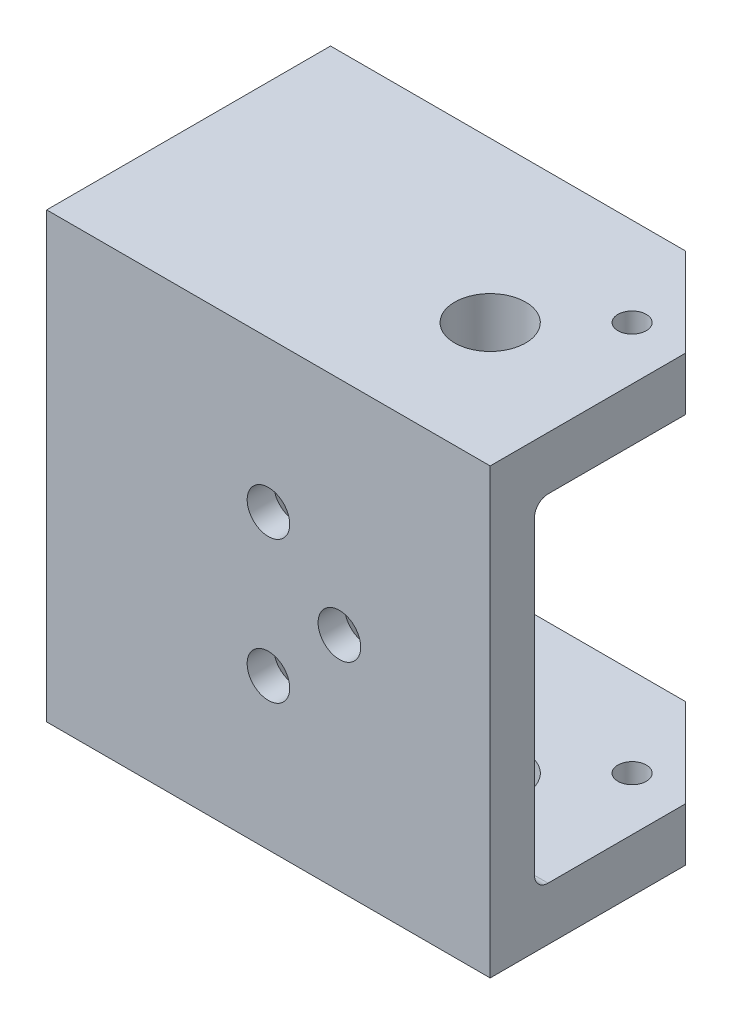
SolidWorks part; units mm, degrees
ref_plane "Front Plane" through (0, 0, 0) normal (0, 0, 1) x (1, 0, 0)
ref_plane "Top Plane" through (0, 0, 0) normal (0, 1, 0) x (1, 0, 0)
ref_plane "Right Plane" through (0, 0, 0) normal (1, 0, 0) x (0, 0, -1)
sketch "Sketch1" plane through (0, 0, 0) normal (0, 0, 1) x (1, 0, 0)
  line L1 (-12.5, 12.5) -> (12.5, 12.5)
  line L2 (-12.5, 12.5) -> (-12.5, -12.5)
  line L3 (-12.5, -12.5) -> (12.5, -12.5)
  line L4 (12.5, 12.5) -> (12.5, -12.5)
  line L5 (-12.5, 12.5) -> (12.5, -12.5) construction
  line L6 (-12.5, -12.5) -> (12.5, 12.5) construction
  point P0 (0, 0)
  dimension "D1" = 25
  dimension "D2" = 25
extrude "Boss-Extrude1" add sketch "Sketch1" along normal blind 2.5
sketch "Sketch2" plane through (0, 0, 0) normal (0, 0, -1) x (-1, 0, 0)
  line L0 (-12.5, -12.5) -> (-12.5, 12.5) construction
  line L1 (12.5, 12.5) -> (-12.5, 12.5)
  line L2 (12.5, 12.5) -> (12.5, 9.5)
  line L3 (12.5, 9.5) -> (-12.5, 9.5)
  line L4 (-12.5, 12.5) -> (-12.5, 9.5)
  line L5 (12.5, 0) -> (-12.5, 0) construction
  line L6 (12.5, 12.5) -> (12.5, -12.5) construction
  line L7 (12.5, -9.5) -> (-12.5, -9.5)
  line L8 (-12.5, -12.5) -> (-12.5, -9.5)
  line L9 (12.5, -12.5) -> (-12.5, -12.5)
  line L10 (12.5, -12.5) -> (12.5, -9.5)
  dimension "D1" = 3
extrude "Boss-Extrude2" add sketch "Sketch2" along normal blind 13.5
sketch "Sketch10" plane through (0, -12.5, 0) normal (0, -1, 0) x (1, 0, 0)
  line L0 (12.5, 2.5) -> (12.5, -13.5) construction
  line L2 (-12.5, 2.5) -> (12.5, 2.5) construction
  line L3 (12.5, -13.5) -> (-12.5, -13.5) construction
  line L4 (12.5, 2.5) -> (12.5, -13.5) construction
  circle A0 centre (5.5, -4.5) radius 2
  circle A1 centre (9.5, -8.5) radius 0.8
  dimension "D1" = 1.6
  dimension "D2" = 4
  dimension "D3" = 7
  dimension "D4" = 7
  dimension "D5" = 5
  dimension "D6" = 3
extrude "Cut-Extrude1" cut sketch "Sketch10" against normal through all contours A0 region at (5.5, -12.5, -4.5)
extrude "Cut-Extrude2" cut sketch "Sketch10<3>" against normal through all contours A1 region at (9.5, -12.5, -8.5)
sketch "Sketch10<3>" plane through (0, -12.5, 0) normal (0, -1, 0) x (1, 0, 0) same geometry as "Sketch10"
fillet "Fillet1" radius 0.762 2 edges at (0, -9.5, 0) (0, 9.5, 0)
chamfer "Chamfer1" distance 5 angle 45 2 edges at (12.5, -11, -13.5) (12.5, 11, -13.5)
sketch "Sketch12" plane through (0, 0, 0) normal (0, 0, -1) x (-1, 0, 0)
  line L0 (-13.6435, 0) -> (16.7073, 0) construction
hole_wizard "CSK for M2 Flat Head Machine Screw1" positions "Sketch13" profile "Sketch14" countersink size "M2" standard "ANSI Metric" end condition through all
sketch "Sketch13" plane through (0, 0, 0) normal (0, 0, -1) x (-1, 0, 0)
  line L0 (-13.6435, 0) -> (16.7073, 0) construction
  line L2 (-13.3169, 0) -> (20.491, 0) construction
  line L3 (-12.5, -8.738) -> (-12.5, 8.738) construction
  point P0 (0, 4)
  point P14 (0, -4)
  point P17 (-4, 0)
  dimension "D1" = 4
  dimension "D2" = 12.5
  dimension "D4" = 4
sketch "Sketch14" plane through (0, 4, 0) normal (1, 0, 0) x (0, 1, 0)
  line L0 (0, 0) -> (0, 2.5)
  line L1 (0, 2.5) -> (1.2, 2.5)
  line L2 (1.2, 2.5) -> (1.2, 1)
  line L3 (1.2, 1) -> (2.2, 0)
  line L5 (2.2, 0) -> (0, 0)
  line L6 (-1.2, 1) -> (-2.2, 0) construction
  line L11 (0, -6.35) -> (0, 107.95) construction
  dimension "Thru Hole Dia." = 2.4
  dimension "Thru Hole Depth" = 2.5
  dimension "Near C'Sink Dia." = 4.4
  dimension "Near C'Sink Angle" = 90
